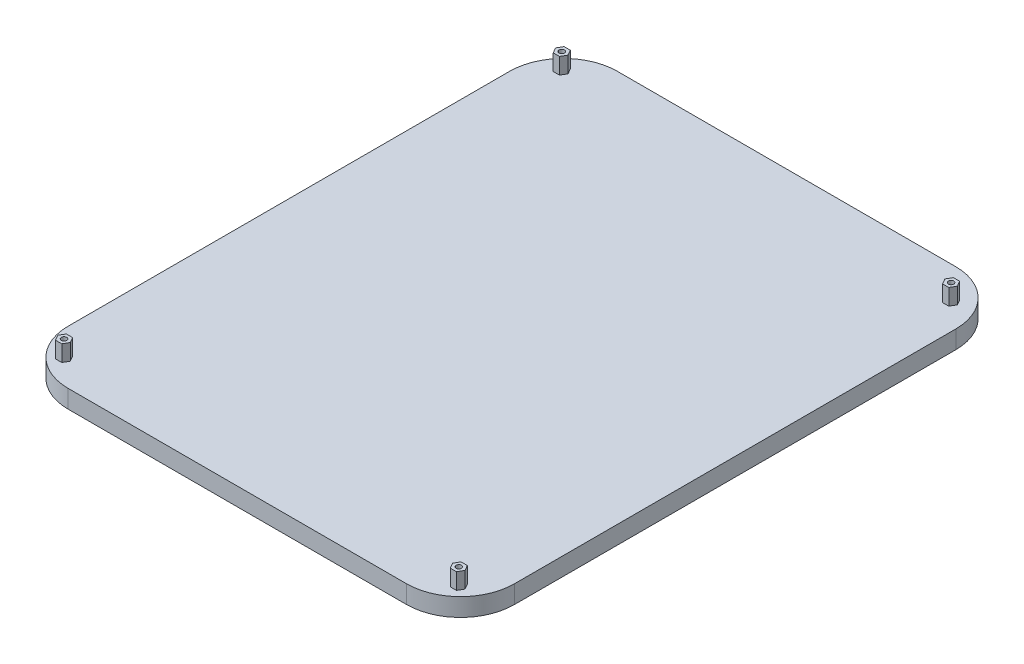
SolidWorks part; units mm, degrees
ref_plane "Front Plane" through (0, 0, 0) normal (0, 0, 1) x (1, 0, 0)
ref_plane "Top Plane" through (0, 0, 0) normal (0, 1, 0) x (1, 0, 0)
ref_plane "Right Plane" through (0, 0, 0) normal (1, 0, 0) x (0, 0, -1)
sketch "Sketch1" plane through (0, 0, 0) normal (0, 1, 0) x (1, 0, 0)
  line L1 (-46.9525, -76.2) -> (46.9525, -76.2)
  line L2 (-61.9125, -61.24) -> (-61.9125, 61.24)
  line L3 (-46.9525, 76.2) -> (46.9525, 76.2)
  line L4 (61.9125, -61.24) -> (61.9125, 61.24)
  line L5 (-61.9125, -76.2) -> (61.9125, 76.2) construction
  line L6 (-61.9125, 76.2) -> (61.9125, -76.2) construction
  arc A0 (46.9525, 76.2) -> (61.9125, 61.24) centre (46.9525, 61.24) cw
  arc A4 (-61.9125, 61.24) -> (-46.9525, 76.2) centre (-46.9525, 61.24) cw
  arc A5 (-46.9525, -76.2) -> (-61.9125, -61.24) centre (-46.9525, -61.24) cw
  arc A6 (46.9525, -76.2) -> (61.9125, -61.24) centre (46.9525, -61.24) ccw
  point P0 (0, 0)
  dimension "D3" = 14.96
  dimension "D5" = 14.96
  dimension "D4" = 14.96
  dimension "D6" = 14.96
  dimension "D1" = 123.825
  dimension "D2" = 152.4
extrude "Floor" add sketch "Sketch1" along normal blind 5
sketch "Sketch2" plane through (0, 5, 0) normal (0, 1, 0) x (1, 0, 0)
  line L0 (46.9525, 76.2) -> (-46.9525, 76.2) construction
  line L1 (53.7435, -70.874) -> (55.4755, -70.874)
  line L2 (55.4755, -70.874) -> (56.3416, -69.374)
  line L3 (56.3416, -69.374) -> (55.4755, -67.874)
  line L4 (55.4755, -67.874) -> (53.7435, -67.874)
  line L5 (53.7435, -67.874) -> (52.8774, -69.374)
  line L6 (52.8774, -69.374) -> (53.7435, -70.874)
  line L7 (-61.9125, 61.24) -> (-61.9125, -61.24) construction
  line L8 (-46.9525, -76.2) -> (46.9525, -76.2) construction
  line L9 (61.9125, -61.24) -> (61.9125, 61.24) construction
  line L10 (55.4755, 68.739) -> (53.7435, 68.739)
  line L11 (53.7435, 68.739) -> (52.8774, 67.239)
  line L12 (52.8774, 67.239) -> (53.7435, 65.739)
  line L13 (53.7435, 65.739) -> (55.4755, 65.739)
  line L14 (55.4755, 65.739) -> (56.3416, 67.239)
  line L15 (56.3416, 67.239) -> (55.4755, 68.739)
  line L16 (-54.0615, 67.239) -> (-53.1954, 68.739)
  line L17 (-53.1954, 68.739) -> (-54.0615, 70.239)
  line L18 (-54.0615, 70.239) -> (-55.7935, 70.239)
  line L19 (-55.7935, 70.239) -> (-56.6596, 68.739)
  line L20 (-56.6596, 68.739) -> (-55.7935, 67.239)
  line L21 (-55.7935, 67.239) -> (-54.0615, 67.239)
  line L23 (-53.1954, -69.374) -> (-54.0615, -67.874)
  line L24 (-54.0615, -67.874) -> (-55.7935, -67.874)
  line L25 (-55.7935, -67.874) -> (-56.6596, -69.374)
  line L26 (-56.6596, -69.374) -> (-55.7935, -70.874)
  line L27 (-55.7935, -70.874) -> (-54.0615, -70.874)
  line L28 (-54.0615, -70.874) -> (-53.1954, -69.374)
  circle A0 centre (54.6095, -69.374) radius 1.5 construction
  circle A1 centre (-54.9275, 68.739) radius 1.5 construction
  circle A2 centre (54.6095, 67.239) radius 1.5 construction
  circle A3 centre (-54.9275, -69.374) radius 1.5 construction
  dimension "D3" = 3
  dimension "D6" = 3
  dimension "D9" = 3
  dimension "D12" = 3
  dimension "D1" = 6.826
  dimension "D2" = 7.303
  dimension "D4" = 7.303
  dimension "D5" = 7.461
  dimension "D7" = 6.985
  dimension "D8" = 7.461
  dimension "D10" = 6.826
  dimension "D11" = 6.985
extrude "Pillars" add sketch "Sketch2" along normal blind 4.5
sketch "Sketch4" plane through (0, 9.5, 0) normal (0, 1, 0) x (1, 0, 0)
  line L2 (52.8774, 67.239) -> (56.3416, 67.239) construction
  line L3 (54.6095, 68.739) -> (54.6095, 65.739) construction
  line L4 (55.4755, 68.739) -> (53.7435, 68.739) construction
  line L5 (53.7435, 65.739) -> (55.4755, 65.739) construction
  circle A0 centre (54.6072, 67.2324) radius 0.75
  dimension "D1" = 1.5
extrude "Cut-Extrude2" cut sketch "Sketch4" against normal blind 5
sketch "Sketch5" plane through (0, 9.5, 0) normal (0, 1, 0) x (1, 0, 0)
  line L0 (-56.6596, -69.374) -> (-53.1954, -69.374) construction
  line L1 (-54.9275, -67.874) -> (-54.9275, -70.874) construction
  line L2 (-54.0615, -67.874) -> (-55.7935, -67.874) construction
  line L3 (-55.7935, -70.874) -> (-54.0615, -70.874) construction
  circle A0 centre (-54.9275, -69.374) radius 0.75
  dimension "D1" = 1.5
extrude "Cut-Extrude3" cut sketch "Sketch5" against normal blind 5
sketch "Sketch6" plane through (0, 9.5, 0) normal (0, 1, 0) x (1, 0, 0)
  line L0 (-56.6596, 68.739) -> (-53.1954, 68.739) construction
  line L1 (-54.9275, 70.239) -> (-54.9275, 67.239) construction
  line L2 (-54.0615, 70.239) -> (-55.7935, 70.239) construction
  line L3 (-55.7935, 67.239) -> (-54.0615, 67.239) construction
  circle A0 centre (-54.9275, 68.739) radius 0.75
  dimension "D1" = 1.5
extrude "Cut-Extrude4" cut sketch "Sketch6" against normal blind 5
sketch "Sketch3" plane through (0, 9.5, 0) normal (0, 1, 0) x (1, 0, 0)
  circle A0 centre (54.6095, -69.374) radius 0.75
  dimension "D1" = 1.5
extrude "Cut-Extrude1" cut sketch "Sketch3" against normal blind 5
sketch "Sketch9" plane through (0, 5, 0) normal (0, 1, 0) x (1, 0, 0)
  line L0 (-61.9125, 0) -> (61.9125, 0) construction
  line L1 (-61.9125, 61.24) -> (-61.9125, -61.24) construction
  line L2 (61.9125, -61.24) -> (61.9125, 61.24) construction
  line L3 (0, 76.2) -> (0, -76.2) construction
  line L4 (46.9525, 76.2) -> (-46.9525, 76.2) construction
  line L5 (-46.9525, -76.2) -> (46.9525, -76.2) construction
